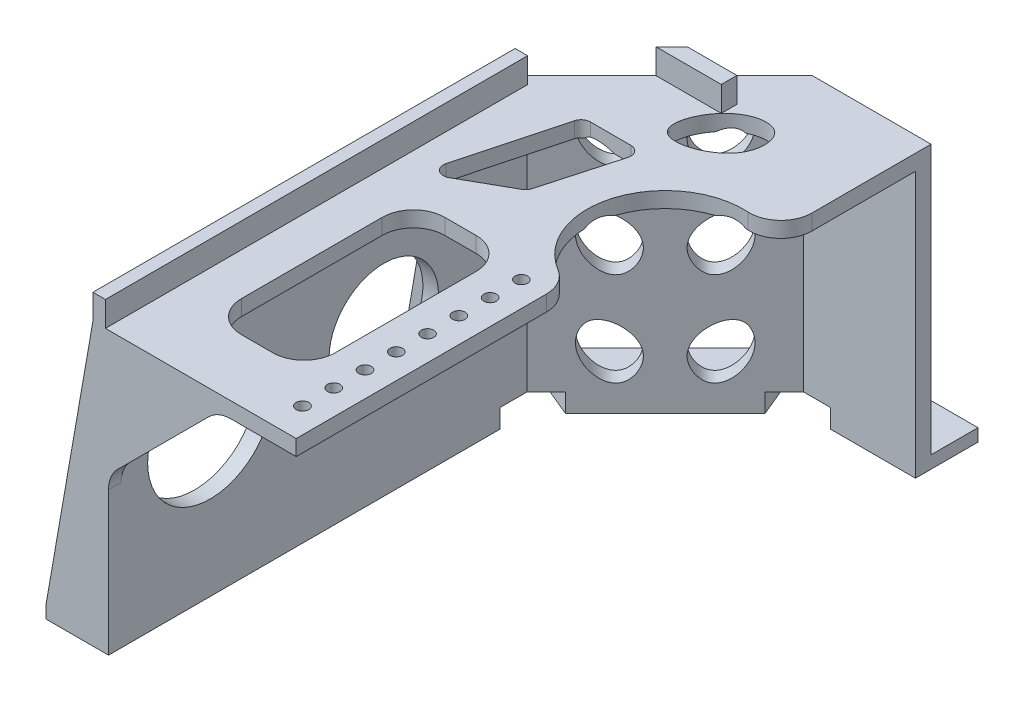
SolidWorks part; units mm, degrees
material "ABS"
ref_plane "前视基准面" through (0, 0, 0) normal (0, 0, 1) x (1, 0, 0)
ref_plane "上视基准面" through (0, 0, 0) normal (0, 1, 0) x (1, 0, 0)
ref_plane "右视基准面" through (0, 0, 0) normal (1, 0, 0) x (0, 0, -1)
sketch "草图1" plane through (0, 0, 0) normal (0, 1, 0) x (1, 0, 0)
  line L1 (-50, -99) -> (50, -99)
  line L2 (-50, -99) -> (-50, 99)
  line L3 (-50, 99) -> (50, 99)
  line L4 (50, -99) -> (50, 99)
  line L5 (-50, -99) -> (50, 99) construction
  line L6 (-50, 99) -> (50, -99) construction
  point P0 (0, 0)
  dimension "D1" = 198
  dimension "D2" = 100
extrude "凸台-拉伸1" add sketch "草图1" along normal blind 90
sketch "草图2" plane through (0, 90, 0) normal (0, 1, 0) x (1, 0, 0)
  line L0 (50, 89) -> (10, 89) construction
  line L1 (50, -99) -> (50, 99) construction
  line L2 (-40, 39) -> (-40, -99) construction
  line L3 (-50, -99) -> (50, -99) construction
  line L4 (50, 99) -> (-50, 99) construction
  line L5 (-50, 99) -> (-50, -99) construction
  line L6 (-40, 39) -> (10, 89) construction
  line L7 (-35, 36.9289) -> (12.0711, 84)
  line L8 (-37.1242, 34.8047) -> (13.5355, 85.4645) construction
  line L9 (-40, -99) -> (-50, -99)
  line L10 (-50, -99) -> (-50, 99)
  line L11 (-50, 99) -> (50, 99)
  line L12 (50, 99) -> (50, 89)
  line L13 (50, 84) -> (12.0711, 84)
  line L14 (-35, 36.9289) -> (-35, -99)
  line L15 (-35, 14.8579) -> (-35, -99) construction
  line L16 (50, 84) -> (24.1421, 84) construction
  line L17 (50, 84) -> (50, 89)
  line L18 (-40, -99) -> (-35, -99)
  line L19 (50, 89) -> (24.1421, 89) construction
  line L20 (-40, 14.8579) -> (-40, -99) construction
  line L21 (-40.6597, 38.3403) -> (10, 89) construction
  point P14 (-40, 25.5398)
  point P26 (14.133, 79)
  point P32 (-39.0303, 25.5398)
  dimension "D1" = 10
  dimension "D2" = 10
  dimension "D3" = 50
  dimension "D4" = 5
  dimension "D7" = 50
  dimension "D5" = 5
  dimension "D6" = 5
extrude "切除-拉伸4" cut sketch "草图2" against normal blind 86
sketch "草图5" plane through (0, 4, 0) normal (0, 1, 0) x (1, 0, 0)
  line L0 (-35, 36.9289) -> (12.0711, 84) construction
  line L1 (-35, 36.9289) -> (12.0711, 84) construction
  line L9 (-50, 43.1421) -> (5.8579, 99)
  line L10 (-45.6066, 47.5355) -> (1.4645, 94.6066) construction
  line L11 (-50, 99) -> (-50, -99) construction
  line L12 (-50, 43.1421) -> (-50, 99)
  line L13 (-50, 99) -> (5.8579, 99)
  line L14 (50, 99) -> (-50, 99) construction
  point P5 (6.1377, 89)
  point P15 (-48.8239, 34.3183)
  dimension "D1" = 15
extrude "切除-拉伸5" cut sketch "草图5" against normal through all
sketch "草图6" plane through (0, 0, 0) normal (0, -1, 0) x (1, 0, 0)
  line L3 (-30, 99) -> (50, 99)
  line L4 (50, 99) -> (50, -79)
  line L6 (50, -79) -> (14.1421, -79)
  line L7 (14.1421, -79) -> (-30, -34.8579)
  line L8 (-30, -34.8579) -> (-30, 99)
  line L9 (50, -79) -> (14.1421, -79)
  line L10 (14.1421, -79) -> (-30, -34.8579)
  line L11 (-30, -34.8579) -> (-30, 99)
  dimension "D1" = 20
extrude "切除-拉伸6" cut sketch "草图6" against normal blind 85
sketch "草图7" plane through (0, 90, 0) normal (0, 1, 0) x (1, 0, 0)
  line L0 (50, 99) -> (5.8579, 99) construction
  line L1 (-50, 43.1421) -> (-50, -99) construction
  line L2 (30, -12.6854) -> (30, -99)
  line L3 (-35, -99) -> (50, -99) construction
  line L4 (30, -99) -> (50, -99)
  line L5 (50, -99) -> (50, -10.9317)
  line L6 (50, -99) -> (50, 84) construction
  arc A0 (50, -10.9317) -> (30, -12.6854) centre (38, 11) ccw
  point P11 (50, -99)
  point P15 (50, -99)
  dimension "D1" = 88
  dimension "D3" = 50
  dimension "D2" = 88
  dimension "D4" = 20
extrude "切除-拉伸7" cut sketch "草图7" against normal through all
fillet "圆角1" radius 10 2 edges at (30, 87.5, 12.6854) (50, 87.5, -32.9317)
sketch "草图8" plane through (0, 4, 0) normal (0, 1, 0) x (1, 0, 0)
  line L0 (-40, -99) -> (-40, 39) construction
  line L1 (-50, -99) -> (-35, -99) construction
  line L2 (50, 99) -> (5.8579, 99) construction
  line L3 (50, 89) -> (10, 89) construction
  line L4 (50, 84) -> (50, 99) construction
  line L6 (-11.4645, 60.4645) -> (-22.0711, 71.0711) construction
  line L7 (-42.9289, 36.0711) -> (12.9289, 91.9289)
  line L8 (-40, 39) -> (10, 89) construction
  line L9 (-35, 36.9289) -> (12.0711, 84) construction
  line L10 (-50, 43.1421) -> (5.8579, 99) construction
  line L11 (-50, 43.1421) -> (-50, -99) construction
  circle A0 centre (-40, -61) radius 1.65
  circle A1 centre (-40, -11) radius 1.5
  circle A2 centre (40, 89) radius 1.65
  circle A3 centre (-25.6066, 53.3934) radius 1.65
  circle A4 centre (-4.3934, 74.6066) radius 1.65
  dimension "D2" = 3.3
  dimension "D3" = 38
  dimension "D4" = 50
  dimension "D5" = 3
  dimension "D6" = 3.3
  dimension "D7" = 10
  dimension "D8" = 3.3
  dimension "D9" = 15
  dimension "D10" = 10
  dimension "D11" = 10
  dimension "D1" = 10
extrude "切除-拉伸8" cut sketch "草图8" against normal through all
sketch "草图9" plane through (0, 4, 0) normal (0, 1, 0) x (1, 0, 0)
  line L0 (-35, -99) -> (-35, 36.9289) construction
  line L1 (-50, -99) -> (-35, -99)
  line L2 (-50, -99) -> (-50, -95)
  line L3 (-50, -95) -> (-35, -95)
  line L4 (-35, -99) -> (-35, -95)
  line L6 (-50, 43.1421) -> (-50, -99) construction
  line L7 (-35, -34) -> (-50, -34)
  line L8 (-35, -34) -> (-35, -38)
  line L9 (-35, -38) -> (-50, -38)
  line L10 (-50, -34) -> (-50, -38)
  line L11 (-20.6569, 72.4853) -> (-10.0503, 61.8787)
  line L12 (-50, 16) -> (-35, 16)
  line L13 (-50, 16) -> (-50, 12)
  line L14 (-50, 12) -> (-35, 12)
  line L15 (-35, 16) -> (-35, 12)
  line L16 (-50, 43.1421) -> (5.8579, 99) construction
  line L17 (-35, 36.9289) -> (12.0711, 84) construction
  line L18 (-10.0503, 61.8787) -> (-12.8787, 59.0503)
  line L19 (-35, 36.9289) -> (12.0711, 84) construction
  line L20 (-12.8787, 59.0503) -> (-23.4853, 69.6569)
  line L21 (-23.4853, 69.6569) -> (-20.6569, 72.4853)
  line L22 (26, 99) -> (26, 84)
  line L23 (50, 99) -> (5.8579, 99) construction
  line L24 (12.0711, 84) -> (50, 84) construction
  line L25 (26, 84) -> (30, 84)
  line L26 (12.0711, 84) -> (50, 84) construction
  line L27 (30, 84) -> (30, 99)
  line L28 (30, 99) -> (26, 99)
  circle A0 centre (-40, -61) radius 1.65 construction
  circle A1 centre (-40, -11) radius 1.5 construction
  circle A2 centre (-4.3934, 74.6066) radius 1.65 construction
  circle A3 centre (40, 89) radius 1.65 construction
  dimension "D1" = 4
  dimension "D2" = 4
  dimension "D3" = 23
  dimension "D4" = 4
  dimension "D5" = 23
  dimension "D6" = 4
  dimension "D7" = 13
  dimension "D8" = 4
  dimension "D9" = 10
extrude "凸台-拉伸2" add sketch "草图9" along normal blind 86
sketch "草图10" plane through (0, 0, -16) normal (0, 0, -1) x (-1, 0, 0)
  line L0 (35, 90) -> (50, 4)
  line L1 (50, 4) -> (50, 90)
  line L2 (50, 90) -> (35, 90)
extrude "切除-拉伸9" cut sketch "草图10" against normal through all
sketch "草图11" plane through (26, 0, 0) normal (-1, 0, 0) x (0, 0, 1)
  line L0 (-99, 90) -> (-84, 90)
  line L1 (-84, 90) -> (-99, 4)
  line L2 (-99, 4) -> (-99, 90)
extrude "切除-拉伸10" cut sketch "草图11" against normal through all
sketch "草图12" plane through (25.9142, 0, -25.9142) normal (0.7071, 0, -0.7071) x (-0.7071, 0, -0.7071)
  line L0 (50.8614, 90) -> (65.8614, 90)
  line L1 (65.8614, 90) -> (65.8614, 4)
  line L2 (65.8614, 4) -> (50.8614, 90)
extrude "切除-拉伸11" cut sketch "草图12" against normal through all
sketch "草图16" plane through (-35, 0, 0) normal (-1, 0, 0) x (0, 0, 1)
  line L0 (66.5, 90) -> (66.5, 4) construction
  line L1 (95, 90) -> (38, 90) construction
  line L2 (95, 4) -> (38, 4) construction
  line L3 (38, 47) -> (95, 47) construction
  line L4 (38, 90) -> (38, 4) construction
  line L5 (95, 4) -> (95, 90) construction
  line L6 (-12, 47) -> (34, 47) construction
  line L7 (-12, 90) -> (-12, 4) construction
  line L8 (34, 90) -> (34, 4) construction
  line L9 (11, 90) -> (11, 4) construction
  line L10 (34, 90) -> (-12, 90) construction
  line L11 (-12, 4) -> (34, 4) construction
  circle A0 centre (66.5, 47) radius 20
  circle A1 centre (11, 47) radius 17.5
  dimension "D1" = 35
  dimension "D2" = 40
extrude "切除-拉伸12" cut sketch "草图16" against normal through all
sketch "草图17" plane through (0, 90, 0) normal (0, 1, 0) x (1, 0, 0)
  line L0 (-35, -99) -> (30, -99) construction
  line L1 (-17.5, -79) -> (12.5, -79)
  line L2 (-17.5, -79) -> (-17.5, -14)
  line L3 (-17.5, -14) -> (12.5, -14)
  line L4 (12.5, -79) -> (12.5, -14)
  line L5 (30, -19.0167) -> (30, -99) construction
  dimension "D1" = 20
  dimension "D2" = 30
  dimension "D3" = 17.5
  dimension "D4" = 65
extrude "切除-拉伸13" cut sketch "草图17" against normal through all
fillet "圆角2" radius 10 4 edges at (12.5, 87.5, 14) (12.5, 87.5, 79) (-17.5, 87.5, 79) (-17.5, 87.5, 14)
sketch "草图18" plane through (0, 85, 0) normal (0, -1, 0) x (1, 0, 0)
  line L2 (-30, 99) -> (5, 99)
  line L3 (-30, 99) -> (-30, 95)
  line L4 (-30, 95) -> (5, 95)
  line L5 (5, 99) -> (5, 95)
  dimension "D1" = 35
  dimension "D2" = 4
extrude "凸台-拉伸4" add sketch "草图18" along normal blind 35
sketch "草图19" plane through (0, 0, 99) normal (0, 0, 1) x (1, 0, 0)
  line L0 (5, 85) -> (-30, 50)
  line L1 (-30, 50) -> (5, 50)
  line L2 (5, 50) -> (-30, 50) construction
  line L3 (5, 50) -> (5, 85) construction
  line L4 (5, 50) -> (5, 85)
extrude "切除-拉伸14" cut sketch "草图19" against normal blind 4
fillet "圆角3" radius 10 2 edges at (-30, 50, 97) (5, 85, 97)
sketch "草图20" plane through (0, 90, 0) normal (0, 1, 0) x (1, 0, 0)
  line L0 (-12.9323, 35.6949) -> (6.269, 35.6949)
  line L1 (6.269, 35.6949) -> (-1.7956, 6.701)
  line L2 (-1.7956, 6.701) -> (-24.008, -5.8438)
  line L3 (-24.008, -5.8438) -> (-12.9323, 35.6949)
  spline S0 degree 3 poles (-2.4228, 38.5236) (6.9467, 63.0254) (23.5714, 65.1737) (24.8494, 47.282) (-2.4228, 38.5236) (6.9467, 63.0254) (23.5714, 65.1737) knots -0.810079 -0.633661 -0.299557 0 0.189921 0.366339 0.700443 1 1.189921 1.366339 1.700443 only from (10.6853, 61.4245) to (10.6853, 61.4245)
extrude "切除-拉伸15" cut sketch "草图20" against normal through all
fillet "圆角4" radius 3 4 edges at (-1.7956, 87.5, -6.701) (6.269, 87.5, -35.6949) (-12.9323, 87.5, -35.6949) (-24.008, 87.5, 5.8438)
sketch "草图21" plane through (0, 0, 0) normal (0, -1, 0) x (1, 0, 0)
  line L0 (-30, -34.8579) -> (-50, -43.1421) construction
  line L1 (-7.9289, -56.9289) -> (-22.0711, -71.0711) construction
  line L2 (-30, -26.1987) -> (-53.0615, -35.7511)
  line L3 (-23.8771, -40.9808) -> (-46.9385, -50.5332)
  line L4 (-33.0615, -27.4668) -> (-53.0615, -35.7511) construction
  line L5 (-30, 95) -> (-30, -34.8579) construction
  line L6 (-26.9385, -42.2489) -> (-46.9385, -50.5332) construction
  line L7 (-30, -34.8579) -> (14.1421, -79) construction
  line L8 (-53.0615, -35.7511) -> (-46.9385, -50.5332)
  line L9 (-30, -26.1987) -> (-23.8771, -40.9808)
  line L10 (-50, -43.1421) -> (5.8579, -99) construction
  line L11 (22.8013, -79) -> (13.2489, -102.0615)
  line L12 (13.2489, -102.0615) -> (-1.5332, -95.9385)
  line L13 (8.0192, -72.8771) -> (-1.5332, -95.9385)
  line L14 (22.8013, -79) -> (8.0192, -72.8771)
  dimension "D1" = 8
  dimension "D2" = 8
extrude "切除-拉伸16" cut sketch "草图21" against normal blind 6
fillet "圆角5" radius 3 4 edges at (-0.2651, 2, -92.8771) (14.517, 2, -99) (-50, 2, -34.483) (-43.8771, 2, -49.2651)
sketch "草图22" plane through (-35.9645, 0, -35.9645) normal (-0.7071, 0, -0.7071) x (-0.7071, 0, 0.7071)
  line L0 (-34.6482, 90) -> (-34.6482, 4) construction
  line L1 (-32.6482, 90) -> (-36.6482, 90) construction
  line L2 (-32.6482, 4) -> (-36.6482, 4) construction
  spline S0 degree 3 poles (-23.6469, 63.4394) (-34.0626, 79.1399) (-17.5748, 90.1739) (-12.0352, 76.3232) (-23.6469, 63.4394) (-34.0626, 79.1399) (-17.5748, 90.1739) knots -0.669362 -0.524971 -0.205707 0 0.330638 0.475029 0.794293 1 1.330638 1.475029 1.794293 only from (-29.6704, 76.6785) to (-29.6704, 76.6785)
  spline S1 degree 3 poles (-23.6469, 33.4394) (-34.0626, 49.1399) (-17.5748, 60.1739) (-12.0352, 46.3232) (-23.6469, 33.4394) (-34.0626, 49.1399) (-17.5748, 60.1739) knots -0.669362 -0.524971 -0.205707 0 0.330638 0.475029 0.794293 1 1.330638 1.475029 1.794293 only from (-29.6704, 46.6785) to (-29.6704, 46.6785)
  spline S2 degree 3 poles (-23.6469, 3.4394) (-34.0626, 19.1399) (-17.5748, 30.1739) (-12.0352, 16.3232) (-23.6469, 3.4394) (-34.0626, 19.1399) (-17.5748, 30.1739) knots -0.669362 -0.524971 -0.205707 0 0.330638 0.475029 0.794293 1 1.330638 1.475029 1.794293 only from (-29.6704, 16.6785) to (-29.6704, 16.6785)
  spline S3 degree 3 poles (-45.6496, 3.4394) (-35.2339, 19.1399) (-51.7216, 30.1739) (-57.2613, 16.3232) (-45.6496, 3.4394) (-35.2339, 19.1399) (-51.7216, 30.1739) knots -0.669362 -0.524971 -0.205707 0 0.330638 0.475029 0.794293 1 1.330638 1.475029 1.794293 only from (-39.626, 16.6785) to (-39.626, 16.6785)
  spline S4 degree 3 poles (-45.6496, 33.4394) (-35.2339, 49.1399) (-51.7216, 60.1739) (-57.2613, 46.3232) (-45.6496, 33.4394) (-35.2339, 49.1399) (-51.7216, 60.1739) knots -0.669362 -0.524971 -0.205707 0 0.330638 0.475029 0.794293 1 1.330638 1.475029 1.794293 only from (-39.626, 46.6785) to (-39.626, 46.6785)
  spline S5 degree 3 poles (-45.6496, 63.4394) (-35.2339, 79.1399) (-51.7216, 90.1739) (-57.2613, 76.3232) (-45.6496, 63.4394) (-35.2339, 79.1399) (-51.7216, 90.1739) knots -0.669362 -0.524971 -0.205707 0 0.330638 0.475029 0.794293 1 1.330638 1.475029 1.794293 only from (-39.626, 76.6785) to (-39.626, 76.6785)
extrude "切除-拉伸17" cut sketch "草图22" against normal through all
fillet "圆角6" radius 3 9 edges at (-35, 47, 95) (-35, 47, 38) (-35, 47, 34) (-35, 47, -12) (-35, 47, -16) (-12.8787, 47, -59.0503) (-10.0503, 47, -61.8787) (26, 47, -84) (30, 47, -84)
sketch "草图23" plane through (0, 90, 0) normal (0, 1, 0) x (1, 0, 0)
  line L0 (22, -99) -> (22, -8.2094) construction
  line L1 (-35, -99) -> (30, -99) construction
  line L2 (30, -19.0167) -> (30, -99) construction
  arc A0 (39.4286, 35.9592) -> (25.1429, -10.4405) centre (38, 11) ccw construction
  circle A1 centre (22, -89) radius 2
  circle A2 centre (22, -79) radius 2
  circle A3 centre (22, -69) radius 2
  circle A4 centre (22, -59) radius 2
  circle A5 centre (22, -49) radius 2
  circle A6 centre (22, -39) radius 2
  circle A7 centre (22, -29) radius 2
  circle A8 centre (22, -19) radius 2
  dimension "D2" = 4
  dimension "D3" = 10
  dimension "D1" = 8
  dimension "D4" = 8
extrude "切除-拉伸18" cut sketch "草图23" against normal through all
sketch "草图24" plane through (-35, 0, 0) normal (-1, 0, 0) x (0, 0, 1)
  line L0 (99, 82) -> (-36.9289, 82) construction
  line L1 (99, 90) -> (99, 4) construction
  line L2 (-36.9289, 6) -> (-36.9289, 90) construction
  line L3 (95, 85) -> (-34.8579, 85) construction
  circle A0 centre (89, 82) radius 2
  circle A1 centre (79, 82) radius 2
  circle A2 centre (69, 82) radius 2
  circle A3 centre (59, 82) radius 2
  circle A4 centre (49, 82) radius 2
  circle A5 centre (39, 82) radius 2 construction
  circle A6 centre (29, 82) radius 2
  circle A7 centre (19, 82) radius 2
  circle A8 centre (9, 82) radius 2
  circle A9 centre (-1, 82) radius 2
  dimension "D2" = 4
  dimension "D3" = 10
  dimension "D1" = 3
  dimension "D4" = 10
extrude "切除-拉伸19" cut sketch "草图24" against normal through all
sketch "草图25" plane through (0, 90, 0) normal (0, 1, 0) x (1, 0, 0)
  line L1 (-35, -99) -> (-31, -99)
  line L2 (-35, -99) -> (-35, 36)
  line L3 (-35, 36) -> (-31, 36)
  line L4 (-31, -99) -> (-31, 36)
  dimension "D1" = 135
  dimension "D2" = 4
extrude "凸台-拉伸5" add sketch "草图25" along normal blind 8
sketch "草图26" plane through (0, 90, 0) normal (0, 1, 0) x (1, 0, 0)
  line L0 (-15, 56.9289) -> (-7.9289, 64) construction
  line L1 (-7.9289, 64) -> (7.921, 64)
  line L2 (-7.9289, 64) -> (-7.9289, 59) construction
  line L3 (-7.9289, 59) -> (7.921, 59)
  line L4 (7.921, 64) -> (7.921, 59)
  line L5 (-7.9289, 59) -> (-12.9289, 59)
  line L6 (-35, 36.9289) -> (-15, 56.9289) construction
  line L7 (-12.9289, 59) -> (-7.9289, 64)
  line L8 (33, 84) -> (23, 84) construction
  spline S0 degree 3 poles (23.5714, 65.1737) (6.9467, 63.0254) (-2.4228, 38.5236) (24.8494, 47.282) (23.5714, 65.1737) (6.9467, 63.0254) (-2.4228, 38.5236) knots -0.700443 -0.366339 -0.189921 0 0.299557 0.633661 0.810079 1 1.299557 1.633661 1.810079 only from (10.6853, 61.4245) to (10.6853, 61.4245) construction
  point P12 (10.0988, 61)
  dimension "D1" = 20
  dimension "D2" = 5
extrude "凸台-拉伸6" add sketch "草图26" along normal blind 8
